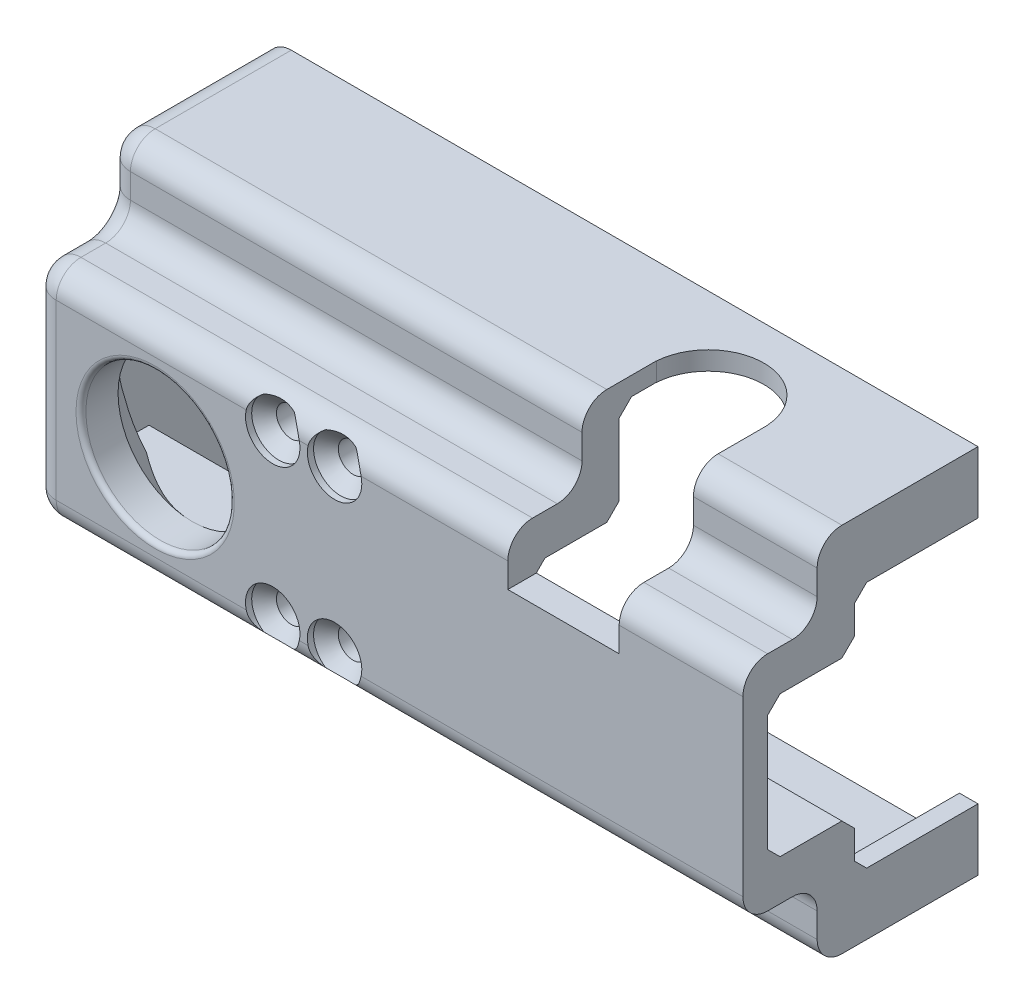
SolidWorks part; units mm, degrees
material "ABS"
ref_plane "Front Plane" through (0, 0, 0) normal (0, 0, 1) x (1, 0, 0)
ref_plane "Top Plane" through (0, 0, 0) normal (0, 1, 0) x (1, 0, 0)
ref_plane "Right Plane" through (0, 0, 0) normal (1, 0, 0) x (0, 0, -1)
sketch "Sketch1" plane through (0, 0, 0) normal (0, 0, 1) x (1, 0, 0)
  line L0 (14.5, -6) -> (14.5, 6)
  line L1 (14.5, 6) -> (0, 6)
  line L2 (0, 6) -> (0, 15)
  line L3 (0, 15) -> (55, 15)
  line L4 (55, 15) -> (55, -15)
  line L5 (14.5, 0) -> (69.4908, 0) construction
  line L6 (0, -15) -> (55, -15)
  line L7 (0, -6) -> (0, -15)
  line L8 (14.5, -6) -> (0, -6)
  point P8 (55, 0)
  dimension "D1" = 12
  dimension "D2" = 30
  dimension "D3" = 14.5
  dimension "D4" = 55
extrude "Boss-Extrude1" add sketch "Sketch1" along normal blind 3
sketch "Sketch2" plane through (0, 0, 0) normal (0, 0, -1) x (-1, 0, 0)
  line L0 (-55, -15) -> (-55, 15) construction
  line L1 (-14.5, -9) -> (-55, -9)
  line L2 (-14.5, -9) -> (-14.5, 9)
  line L3 (-14.5, 9) -> (-55, 9)
  line L4 (-55, -9) -> (-55, 9)
  line L5 (-14.5, -9) -> (-55, 9) construction
  line L6 (-14.5, 9) -> (-55, -9) construction
  line L7 (0, 0) -> (6.435, 0) construction
  line L8 (0, 8.5) -> (0, -8.5) construction
  line L9 (-14.5, 5) -> (-14.5, -5) construction
  point P0 (-34.75, 0)
  dimension "D1" = 18
extrude "Boss-Extrude2" add sketch "Sketch2" against normal blind 9
sketch "Sketch3" plane through (0, 0, 0) normal (0, 0, -1) x (-1, 0, 0)
  line L0 (-55, -15) -> (-55, 15) construction
  line L1 (-55, 5.7) -> (-14.5, 5.7)
  line L2 (-55, 5.7) -> (-55, -5.7)
  line L3 (-55, -5.7) -> (-14.5, -5.7)
  line L4 (-14.5, 5.7) -> (-14.5, -5.7)
  line L5 (-55, 5.7) -> (-14.5, -5.7) construction
  line L6 (-55, -5.7) -> (-14.5, 5.7) construction
  line L7 (-14.5, 5) -> (-14.5, -5) construction
  point P0 (-34.75, 0)
  dimension "D1" = 11.4
extrude "Cut-Extrude1" cut sketch "Sketch3" against normal blind 7
sketch "Sketch4" plane through (0, 0, 0) normal (0, 0, -1) x (-1, 0, 0)
  line L0 (0, 15) -> (-55, 15)
  line L1 (-55, 15) -> (-55, 10)
  line L3 (-55, 5.7) -> (-55, 15) construction
  line L4 (0, 13.5) -> (-53.5, 13.5)
  line L5 (-53.5, 13.5) -> (-53.5, 10)
  line L6 (-55, 10) -> (-53.5, 10)
  line L7 (0, 15) -> (0, 13.5)
  dimension "D1" = 5
  dimension "D2" = 1.5
extrude "Boss-Extrude3" add sketch "Sketch4" along normal blind 10
sketch "Sketch5" plane through (0, 0, 0) normal (0, 0, -1) x (-1, 0, 0)
  line L0 (0, -6) -> (0, -15) construction
  line L1 (0, -10) -> (-14.5, -10)
  line L2 (0, -10) -> (0, 10)
  line L3 (0, 10) -> (-14.5, 10)
  line L4 (-14.5, -10) -> (-14.5, 10)
  line L5 (0, -10) -> (-14.5, 10) construction
  line L6 (0, 10) -> (-14.5, -10) construction
  line L7 (-14.5, 9.5) -> (-14.5, 12) construction
  point P0 (-7.25, 0)
  dimension "D1" = 20
extrude "Cut-Extrude2" cut sketch "Sketch5" against normal blind 1
sketch "Sketch8" plane through (0, 0, 7) normal (0, 0, -1) x (-1, 0, 0)
  line L0 (-14.5, 5.7) -> (-55, 5.7) construction
  line L1 (-14.5, -5.7) -> (-24.5, -5.7)
  line L2 (-14.5, -5.7) -> (-14.5, 5.7)
  line L3 (-14.5, 5.7) -> (-24.5, 5.7)
  line L4 (-24.5, -5.7) -> (-24.5, 5.7)
  line L5 (-14.5, -5.7) -> (-24.5, 5.7) construction
  line L6 (-14.5, 5.7) -> (-24.5, -5.7) construction
  point P0 (-19.5, 0)
  dimension "D1" = 10
extrude "Boss-Extrude4" add sketch "Sketch8" along normal blind 4.7
hole_wizard "M2 Clearance Hole1" positions "Sketch7" profile "Sketch6" hole size "M2" standard "DIN"
sketch "Sketch7" plane through (0, 0, 0) normal (0, 0, -1) x (-1, 0, 0)
  point P0 (-17, -6.5)
  point P1 (-22, 6.5)
  point P4 (-17, 6.5)
  point P7 (-22, -6.5)
sketch "Sketch6" plane through (17, -6.5, 0) normal (1, 0, 0) x (0, 1, 0)
  line L0 (0, 0) -> (0, 10)
  line L1 (0, 10) -> (1.2, 10)
  line L2 (1.2, 10) -> (1.2, 0)
  line L5 (1.2, 0) -> (0, 0)
  line L10 (0, 10) -> (-1.2, 10) construction
  line L11 (0, -6.35) -> (0, 107.95) construction
  dimension "Hole Dia." = 2.4
  dimension "Hole Depth" = 10
  dimension "Drill Angle" = 180
mirror "Mirror1" about plane through (0, 0, 0) normal (0, 1, 0) of "Boss-Extrude3"
chamfer "Chamfer2" distance 0.5 angle 45 6 edges at (23.6972, 5.7, 2.3) (23.6972, -5.7, 2.3) (24.5, 5.7, 4.65) (24.5, 0, 2.3) (24.5, -5.7, 4.65) (24.5, 0, 7)
hole_wizard "CSK for M2 Countersunk Flat Head Screw1" positions "Sketch15" profile "Sketch14" countersink size "M2" standard "DIN" end condition through all
sketch "Sketch15" plane through (0, 0, 9) normal (0, 0, 1) x (1, 0, 0)
  point P0 (17, -6.5)
  point P1 (17, 6.5)
  point P3 (22, 6.5)
  point P5 (22, -6.5)
sketch "Sketch14" plane through (17, -6.5, 9) normal (1, 0, 0) x (0, -1, 0)
  line L0 (0, 0) -> (0, 19)
  line L1 (0, 19) -> (1.2, 19)
  line L2 (1.2, 19) -> (1.2, 1.5)
  line L3 (1.2, 1.5) -> (2.2, 0.5)
  line L4 (2.2, 0.5) -> (2.2, 0)
  line L6 (2.2, 0) -> (0, 0)
  line L7 (-1.2, 1.5) -> (-2.2, 0.5) construction
  line L11 (0, -6.35) -> (0, 107.95) construction
  dimension "Thru Hole Dia." = 2.4
  dimension "Thru Hole Depth" = 19
  dimension "C'Sink Dia." = 4.4
  dimension "C'Sink Angle" = 90
  dimension "Head Clearance" = 0.5
sketch "Sketch16" plane through (0, 0, 0) normal (-1, 0, 0) x (0, 0, 1)
  line L8 (0, 13.5) -> (0, 10)
  line L9 (0, 10) -> (1, 10)
  line L10 (1, 10) -> (1, 6)
  line L11 (1, 6) -> (3, 6)
  line L12 (3, 6) -> (3, 15)
  line L13 (3, 15) -> (-10, 15)
  line L14 (-10, 15) -> (-10, 13.5)
  line L15 (-10, 13.5) -> (0, 13.5)
  line L16 (0, 13.5) -> (0, 10)
  line L17 (0, 10) -> (1, 10)
  line L18 (1, 10) -> (1, 6)
  line L19 (1, 6) -> (3, 6)
  line L20 (3, 6) -> (3, 15)
  line L21 (3, 15) -> (-10, 15)
  line L22 (-10, 15) -> (-10, 13.5)
  line L23 (-10, 13.5) -> (0, 13.5)
  dimension "D1" = 0
extrude "Boss-Extrude5" add sketch "Sketch16" along normal blind 1
mirror "Mirror2" about plane through (0, 0, 0) normal (0, 1, 0) of "Boss-Extrude5"
sketch "Sketch17" plane through (-1, 0, 0) normal (-1, 0, 0) x (0, 0, 1)
  line L1 (-10, 15) -> (3, 15)
  line L2 (-10, 15) -> (-10, -15)
  line L3 (-10, -15) -> (3, -15)
  line L4 (3, 15) -> (3, -15)
extrude "Boss-Extrude6" add sketch "Sketch17" along normal blind 1.5
sketch "Sketch19" plane through (14.5, 0, 0) normal (-1, 0, 0) x (0, 0, 1)
  line L1 (9, 9) -> (3, 9)
  line L2 (9, 9) -> (9, -9)
  line L3 (9, -9) -> (3, -9)
  line L4 (3, 9) -> (3, -9)
extrude "Boss-Extrude7" add sketch "Sketch19" along normal up to surface (17 mm away) up to face at (-2.5, 0, -3.5)
sketch "Sketch20" plane through (0, 0, 3) normal (0, 0, -1) x (-1, 0, 0)
  circle A0 centre (-7.5, 0) radius 6
extrude "Cut-Extrude4" cut sketch "Sketch20" against normal blind 10
sketch "Sketch21" plane through (-1, 0, 0) normal (1, 0, 0) x (0, 0, -1)
  circle A0 centre (5, 0) radius 2.5
  dimension "D1" = 5
extrude "Cut-Extrude5" cut sketch "Sketch21" against normal blind 10
chamfer "Chamfer3" distance 1 angle 45 13 edges at (38.9472, 5.7, 0) (26.25, -13.5, 0) (40, 5.7, 7) (24.75, -5.45, 6.75) (24.75, 5.45, 6.75) (-1, 11.75, 0) (-1, -11.75, 0) (40, -5.7, 7) (38.9472, -5.7, 0) (26.25, 13.5, 0)
fillet "Fillet1" radius 2 13 edges at (26.25, -15, 3) (26.25, 15, 3) (26.25, 9, 9) (26.25, -9, 9) (26.25, 9, 3) (-2.5, -15, -3.5) (-2.5, -12, 3) (-2.5, 15, -3.5) (26.25, -9, 3) (-2.5, 12, 3) (-2.5, -9, 6) (-2.5, 0, 9) (-2.5, 9, 6)
chamfer "Chamfer4" distance 3 angle 45 4 edges
fillet "Fillet2" radius 0.4 1 edges at (1.5, 0, 9)
sketch "Sketch22" plane through (0, 13.5, 0) normal (0, -1, 0) x (1, 0, 0)
  circle A0 centre (40.5, -2.7) radius 4.5
  dimension "D1" = 9
extrude "Cut-Extrude6" cut sketch "Sketch22" against normal blind 10
sketch "Sketch23" plane through (0, 0, 3) normal (0, 0, 1) x (1, 0, 0)
  line L0 (-0.5, 15) -> (37.9388, 15) construction
  line L1 (45, 15) -> (36, 15)
  line L2 (45, 15) -> (45, 5)
  line L3 (45, 5) -> (36, 5)
  line L4 (36, 15) -> (36, 5)
  line L5 (36, 15) -> (36, 13.5) construction
  line L6 (138.5, 5) -> (14.5, 5) construction
extrude "Cut-Extrude7" cut sketch "Sketch23" along normal blind 33 and the other way blind 6
